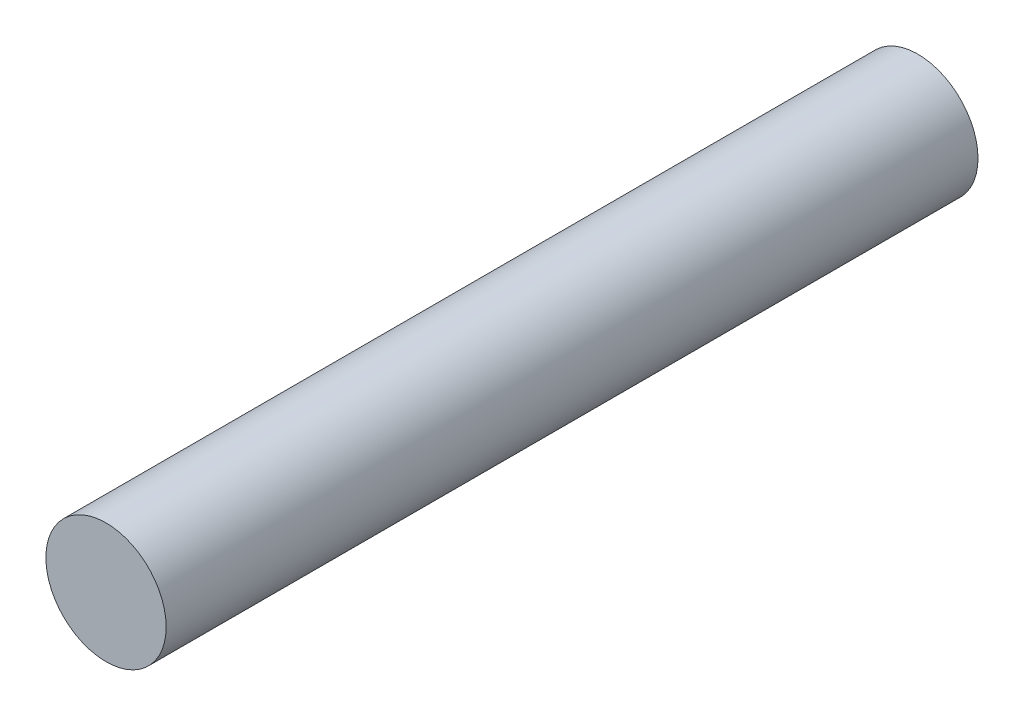
SolidWorks part; units mm, degrees
ref_plane "Front Plane" through (0, 0, 0) normal (0, 0, 1) x (1, 0, 0)
ref_plane "Top Plane" through (0, 0, 0) normal (0, 1, 0) x (1, 0, 0)
ref_plane "Right Plane" through (0, 0, 0) normal (1, 0, 0) x (0, 0, -1)
sketch "Sketch1" plane through (0, 0, 0) normal (0, 0, 1) x (1, 0, 0)
  circle A0 centre (0, 0) radius 25.4
  dimension "D1" = 50.8
extrude "Boss-Extrude1" add sketch "Sketch1" along normal blind 342.9
